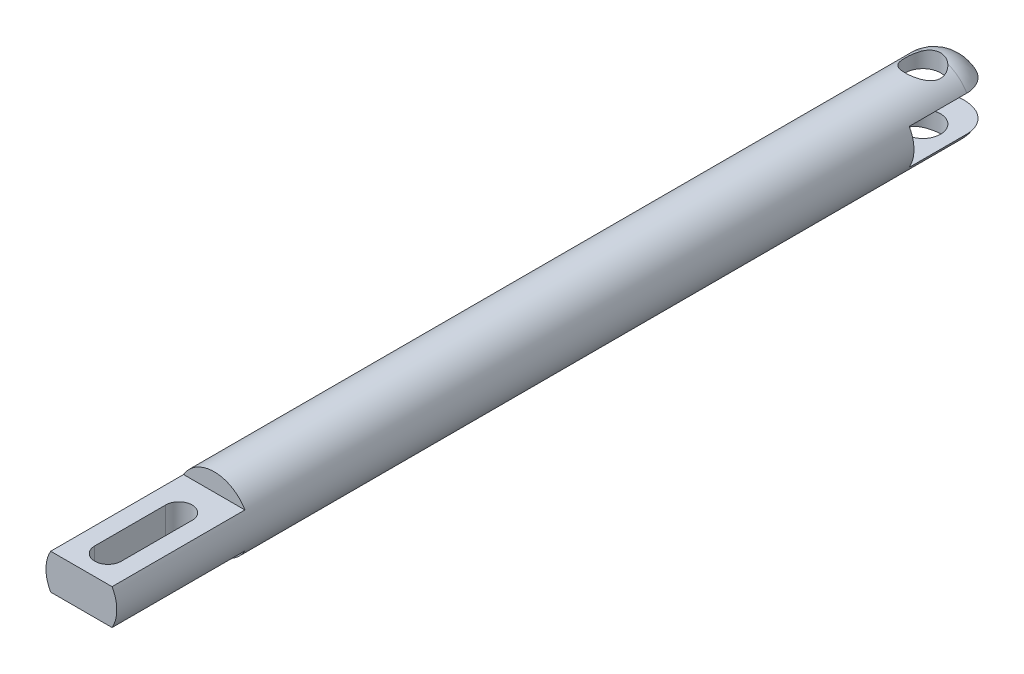
SolidWorks part; units mm, degrees
ref_plane "Płaszczyzna przednia" through (0, 0, 0) normal (0, 0, 1) x (1, 0, 0)
ref_plane "Płaszczyzna górna" through (0, 0, 0) normal (0, 1, 0) x (1, 0, 0)
ref_plane "Płaszczyzna prawa" through (0, 0, 0) normal (1, 0, 0) x (0, 0, -1)
sketch "Szkic1" plane through (0, 0, 0) normal (0, 0, 1) x (1, 0, 0)
  circle A0 centre (0, 0) radius 4
extrude "Dodanie-wyciągnięcie1" add sketch "Szkic1" along normal blind 100
sketch "Szkic3" plane through (0, 0, 0) normal (0, 1, 0) x (1, 0, 0)
  line L0 (4, -100) -> (4, 0) construction
  line L1 (-4, 0) -> (4, 0)
  line L2 (-4, 0) -> (-4, -10)
  line L3 (-4, -10) -> (4, -10)
  line L4 (4, 0) -> (4, -10)
extrude "Wytnij-wyciągnięcie1" cut sketch "Szkic3" along normal blind 2 and the other way blind 2
sketch "Szkic5" plane through (0, -2, 0) normal (0, 1, 0) x (1, 0, 0)
  circle A0 centre (0, -5) radius 2
  dimension "D1" = 4
extrude "Wytnij-wyciągnięcie2" cut sketch "Szkic5" against normal up to next and the other way up to next
fillet "Zaokrąglenie3" radius 3.5 2 edges at (0, -4, 0) (0, 4, 0)
sketch "Szkic6" plane through (0, 0, 0) normal (0, 1, 0) x (1, 0, 0)
  line L0 (-4, -10) -> (-4, -100) construction
  line L1 (4, -100) -> (-4, -100)
  line L2 (4, -100) -> (4, -85)
  line L3 (4, -85) -> (-4, -85)
  line L4 (-4, -100) -> (-4, -85)
extrude "Wytnij-wyciągnięcie3" cut sketch "Szkic6" along normal up to next from offset 2
sketch "Szkic7" plane through (0, 2, 0) normal (0, 1, 0) x (1, 0, 0)
  line L1 (3.4641, -100) -> (-3.4641, -100)
  line L2 (3.4641, -100) -> (3.4641, -85)
  line L3 (3.4641, -85) -> (-3.4641, -85)
  line L4 (-3.4641, -100) -> (-3.4641, -85)
extrude "Wytnij-wyciągnięcie4" cut sketch "Szkic7" against normal up to next from offset 4 offset against normal yes
sketch "Szkic8" plane through (0, 2, 0) normal (0, 1, 0) x (1, 0, 0)
  line L0 (0, -96.9898) -> (0, -88.9898) construction
  line L1 (-1.5, -96.9898) -> (-1.5, -88.9898)
  line L2 (1.5, -96.9898) -> (1.5, -88.9898)
  arc A0 (-1.5, -96.9898) -> (1.5, -96.9898) centre (0, -96.9898) ccw
  arc A1 (1.5, -88.9898) -> (-1.5, -88.9898) centre (0, -88.9898) ccw
  point P3 (0, -92.9898)
extrude "Wytnij-wyciągnięcie5" cut sketch "Szkic8" against normal up to next
